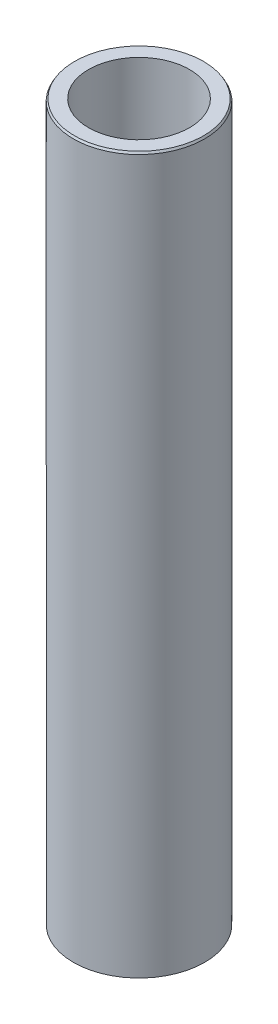
SolidWorks part; units mm, degrees
ref_plane "Front Plane" through (0, 0, 0) normal (0, 0, 1) x (1, 0, 0)
ref_plane "Top Plane" through (0, 0, 0) normal (0, 1, 0) x (1, 0, 0)
ref_plane "Right Plane" through (0, 0, 0) normal (1, 0, 0) x (0, 0, -1)
sketch "Sketch1" plane through (0, 0, 0) normal (0, 1, 0) x (1, 0, 0)
  circle A0 centre (0, 0) radius 55
  dimension "SHAFT_OD" = 110
extrude "Boss-Extrude1" add sketch "Sketch1" along normal blind 600
sketch "Sketch2" plane through (0, 0, 0) normal (0, 1, 0) x (1, 0, 0)
  circle A0 centre (0, 0) radius 42.2828
  dimension "BORE_D" = 84.5656
extrude "Cut-Extrude1" cut sketch "Sketch2" along normal through all
chamfer "Chamfer1" distance 1.7272 angle 30 2 edges at (0, 600, 55) (0, 0, 55) first distance on face at (0, 600, 55) first distance on face at (0, 0, 42.2828)
